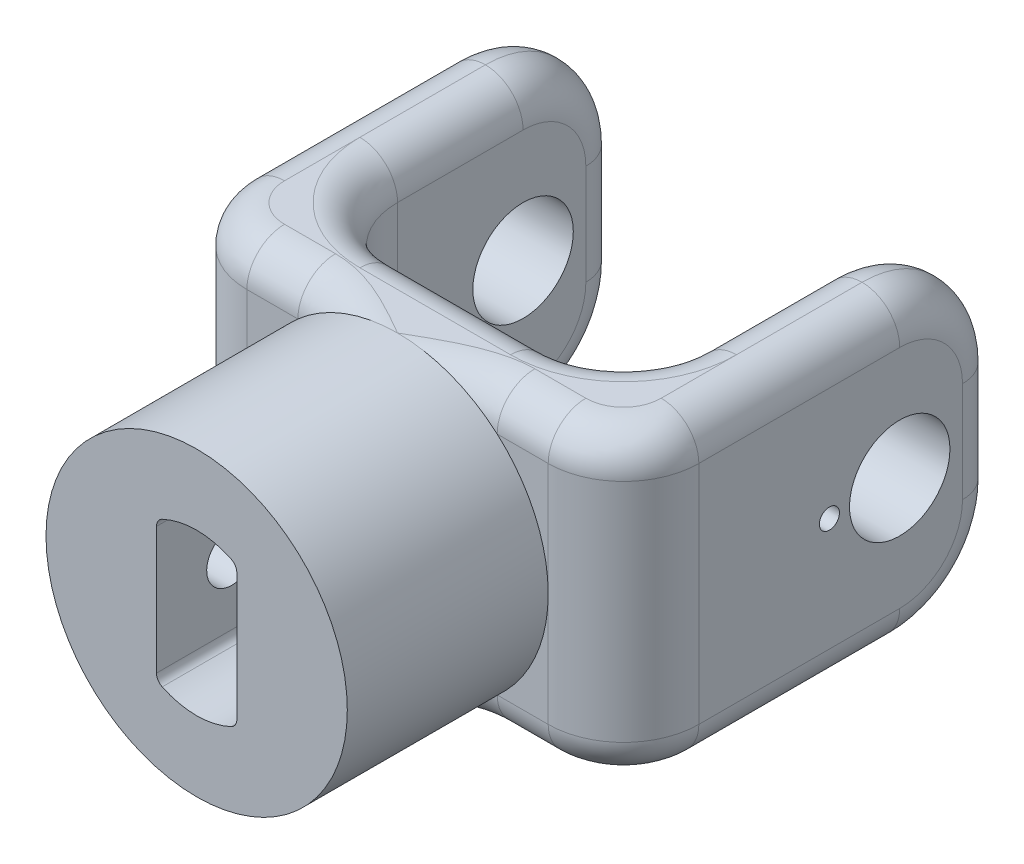
SolidWorks part; units mm, degrees
ref_plane "Front Plane" through (0, 0, 0) normal (0, 0, 1) x (1, 0, 0)
ref_plane "Top Plane" through (0, 0, 0) normal (0, 1, 0) x (1, 0, 0)
ref_plane "Right Plane" through (0, 0, 0) normal (1, 0, 0) x (0, 0, -1)
sketch "Sketch1" plane through (0, 0, 0) normal (0, 1, 0) x (1, 0, 0)
  line L0 (-22.5, 0) -> (-22.5, 37.5)
  line L1 (22.5, 0) -> (22.5, 37.5)
  line L2 (22.5, 37.5) -> (15, 37.5)
  line L3 (15, 37.5) -> (15, 7.5)
  line L4 (-22.5, 37.5) -> (-15, 37.5)
  line L5 (-15, 37.5) -> (-15, 7.5)
  line L6 (-15, 7.5) -> (15, 7.5)
  line L7 (-22.5, 0) -> (22.5, 0)
  dimension "D3" = 7.5
  dimension "D1" = 7.5
  dimension "D2" = 30
  dimension "D4" = 30
extrude "Boss-Extrude1" add sketch "Sketch1" along normal blind 30
fillet "Fillet1" radius 10 4 edges at (18.75, 30, -37.5) (18.75, 0, -37.5) (-18.75, 0, -37.5) (-18.75, 30, -37.5)
sketch "Sketch2" plane through (22.5, 0, 0) normal (1, 0, 0) x (0, 0, -1)
  line L0 (37.5, 20) -> (37.5, 10) construction
  circle A0 centre (27.5, 15) radius 5
  point P7 (37.5, 15)
  dimension "D1" = 10
  dimension "D2" = 10
extrude "Cut-Extrude1" cut sketch "Sketch2" against normal up to surface (45 mm away) up to face at (-22.5, 15, -22.357)
ref_plane "Plane1" through (0, 0, 20) normal (0, 0, 1) x (1, 0, 0)
sketch "Sketch3" plane through (0, 0, 20) normal (0, 0, 1) x (1, 0, 0)
  line L2 (-22.5, 0) -> (22.5, 0) construction
  circle A0 centre (0, 15) radius 15
  dimension "D2" = 30
  dimension "D1" = 15
extrude "Boss-Extrude2" add sketch "Sketch3" against normal up to next
fillet "Fillet2" radius 7.5 2 edges at (-22.5, 15, 0) (22.5, 15, 0)
fillet "Fillet3" radius 7.5 2 edges at (15, 15, -7.5) (-15, 15, -7.5)
fillet "Fillet4" radius 3.75 34 edges at (0, 0, -7.5) (12.8033, 0, -9.6967) (15, 0, -21.25) (15, 2.9289, -34.5711) (22.5, 2.9289, -34.5711) (20.3033, 0, -2.1967) (22.5, 0, -17.5) (-7.5, 0, 0) (7.5, 0, 0) (-20.3033, 0, -2.1967) (-12.8033, 0, -9.6967) (-22.5, 0, -17.5) (-15, 0, -21.25) (-15, 2.9289, -34.5711) (-22.5, 2.9289, -34.5711) (-20.3033, 30, -2.1967) (7.5, 30, 0) (-7.5, 30, 0) (20.3033, 30, -2.1967) (22.5, 30, -17.5) (22.5, 27.0711, -34.5711) (15, 27.0711, -34.5711) (15, 30, -21.25) (12.8033, 30, -9.6967) (0, 30, -7.5) (-12.8033, 30, -9.6967) (-22.5, 30, -17.5) (-15, 30, -21.25) (-15, 27.0711, -34.5711) (-22.5, 27.0711, -34.5711) (-15, 15, -37.5) (15, 15, -37.5) (22.5, 15, -37.5) (-22.5, 15, -37.5)
sketch "Sketch4" plane through (0, 0, 20) normal (0, 0, 1) x (1, 0, 0)
  line L0 (-4, 21.9282) -> (-4, 8.0718)
  line L1 (4, 8.0718) -> (4, 21.9282)
  line L2 (-4, 8.0718) -> (4, 21.9282) construction
  arc A0 (-4, 8.0718) -> (4, 8.0718) centre (0, 15) ccw
  circle A1 centre (0, 15) radius 15 construction
  arc A2 (-9.9216, 26.25) -> (-15, 15) centre (0, 15) ccw construction
  arc A3 (4, 21.9282) -> (-4, 21.9282) centre (0, 15) ccw
  dimension "D1" = 16
  dimension "D2" = 8
extrude "Cut-Extrude2" cut sketch "Sketch4" against normal blind 15 contours A0 L1 A3 L0
sketch "Sketch5" plane through (22.5, 0, 0) normal (1, 0, 0) x (0, 0, -1)
  point P0 (27.5, 15)
sketch "Sketch6" plane through (-22.5, 0, 0) normal (-1, 0, 0) x (0, 0, 1)
  circle A0 centre (-20.5, 15) radius 1
  circle A1 centre (-27.5, 15) radius 5 construction
  point P3 (-27.5, 15)
  dimension "D1" = 2
  dimension "D2" = 7
extrude "Cut-Extrude3" cut sketch "Sketch6" against normal blind 3 contours A0
cosmetic thread "Cosmetic Thread2" parameters "D2"=2.5
mirror "Mirror1" about plane through (0, 0, 0) normal (1, 0, 0) of "Cut-Extrude3"
fillet "Fillet5" radius 1 4 edges at (-4, 21.9282, 12.5) (4, 21.9282, 12.5) (4, 8.0718, 12.5) (-4, 8.0718, 12.5)
sketch "Sketch8" plane through (0, 0, 0) normal (1, 0, 0) x (0, 0, -1)
  line L0 (-12.5, 30) -> (-12.5, 0) construction
  line L1 (0, 30) -> (-20, 30) construction
  line L2 (-20, 0) -> (0, 0) construction
  line L3 (-20, 30) -> (-20, 0) construction
  circle A0 centre (-12.5, 15) radius 2.5
  dimension "D1" = 5
  dimension "D2" = 7.5
extrude "Cut-Extrude4" cut sketch "Sketch8" against normal through all
cosmetic thread "Cosmetic Thread3" parameters "D2"=6
equation "\"D1@Boss-Extrude1\"=30"
equation "\"D1@Fillet1\"=\"shaft outer diameter\"/2"
equation "\"D3@Sketch1\"=\"u_joint thickness\""
equation "\"D1@Sketch1\"=\"u_joint thickness\""
equation "\"D2@Sketch1\"=\"u_joint clearance\""
equation "\"D4@Sketch1\"=\"u_joint clearance\""
equation "\"D1@Fillet2\"=\"u_joint thickness\""
equation "\"D1@Fillet3\"=\"u_joint thickness\""
equation "\"D1@Fillet4\"=\"u_joint thickness\"/2"
equation "\"D1@Sketch2\"=10"
equation "\"short_bearing_outer_width\" = 10mm "
equation "\"shaft inner diameter\"= 15mm "
equation "\"shaft outer diameter\"= 20mm "
equation "\"keyway_height\" = 1.39mm "
equation "\"keyway_width\" = 2.78mm "
equation "\"keyway_length\" = 30mm "
equation "\"steering column length\" = 555mm "
equation "\"u_joint clearance\" = 30mm "
equation "\"u_joint thickness\" = 7.5mm "
equation "\"horizontal shaft length\" = 90mm "
equation "\"pinion width\" = 26.5mm "
equation "\"number of teeth\" = 18mm "
equation "\"D1@Sketch4\"=\"secondary shaft small diameter\""
equation "\"D1@Cut-Extrude2\"=20"
equation "\"column angle\" = 45deg "
equation "\"steering wheel bolt width\" = 6mm "
equation "\"steering wheel bolt length\" = 40mm "
equation "\"bushing length\" = 40mm "
equation "\"bushing thickness\" = 3mm "
equation "\"column bushing diameter\" = \"primary shaft small diameter\" + 4 "
equation "\"column bushing distance\" = \"steering column length\"/4 "
equation "\"D2@Sketch4\"=\"secondary shaft small diameter\"/2"
equation "\"wheel base\" = 1561mm "
equation "\"track\" = 1354mm "
equation "\"turning radius\" = 2000mm "
equation "\"turn to lock\" = 0.75mm "
equation "\"steering arm length\" = 100mm "
equation "\"primary shaft small diameter\" = 16mm "
equation "\"primary shaft large diameter\" = 24mm "
equation "\"secondary shaft small diameter\" = 16mm "
equation "\"secondary shaft large diameter\" = 25mm "
equation "\"pin hole diameter\" = 10mm "
equation "\"rack hole to hole\" = 500mm "
equation "\"rack length\" = \"rack hole to hole\" + \"pin hole diameter\"*2 "
equation "\"max turning angle\" = atn(\"wheel base\" / (\"turning radius\" - 0.5 * \"track\")) "
equation "\"max travel\" = 2 * \"steering arm length\" * sin(0.5 * \"max turning angle\") "
equation "\"pitch diameter\" = \"max travel\"/(pi * \"turn to lock\") "
equation "\"pressure angle\" = 20deg "
equation "\"module\" = \"pitch diameter\" / \"number of teeth\" "
equation "\"tie rod length\" = 305mm "
equation "\"tie rod inner diameter\" = 6.6mm "
equation "\"tie rod outer diameter\" = 8.1mm "
